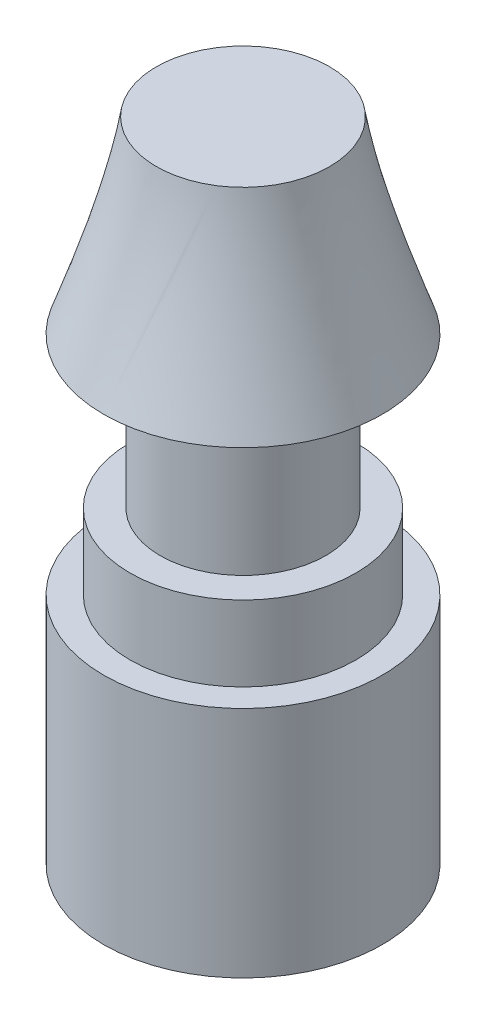
SolidWorks part; units mm, degrees
ref_plane "Front Plane" through (0, 0, 0) normal (0, 0, 1) x (1, 0, 0)
ref_plane "Top Plane" through (0, 0, 0) normal (0, 1, 0) x (1, 0, 0)
ref_plane "Right Plane" through (0, 0, 0) normal (1, 0, 0) x (0, 0, -1)
sketch "Sketch1" plane through (0, 0, 0) normal (0, 1, 0) x (1, 0, 0)
  circle A0 centre (0, 0) radius 1.85
  dimension "D1" = 3.7
extrude "Boss-Extrude1" add sketch "Sketch1" along normal blind 3.1
sketch "Sketch2" plane through (0, 3.1, 0) normal (0, 1, 0) x (1, 0, 0)
  circle A0 centre (0, 0) radius 1.5
  dimension "D1" = 3
extrude "Boss-Extrude2" add sketch "Sketch2" along normal blind 1
sketch "Sketch3" plane through (0, 4.1, 0) normal (0, 1, 0) x (1, 0, 0)
  circle A0 centre (0, 0) radius 1.1
  dimension "D1" = 2.2
extrude "Boss-Extrude3" add sketch "Sketch3" along normal blind 2
sketch "Sketch4" plane through (0, 6.1, 0) normal (0, 1, 0) x (1, 0, 0)
  circle A0 centre (0, 0) radius 1.85
  dimension "D1" = 3.7
ref_plane "Plane1" through (0, 8.6, 0) normal (0, 1, 0) x (1, 0, 0)
sketch "Sketch5" plane through (0, 8.6, 0) normal (0, 1, 0) x (1, 0, 0)
  circle A0 centre (0, 0) radius 1.15
  dimension "D1" = 2.3
loft "Loft1" add profiles "Sketch4", "Sketch5" connector at (0, 6.1, 1.85) connector at (0.6205, 8.6, 0.9683)
